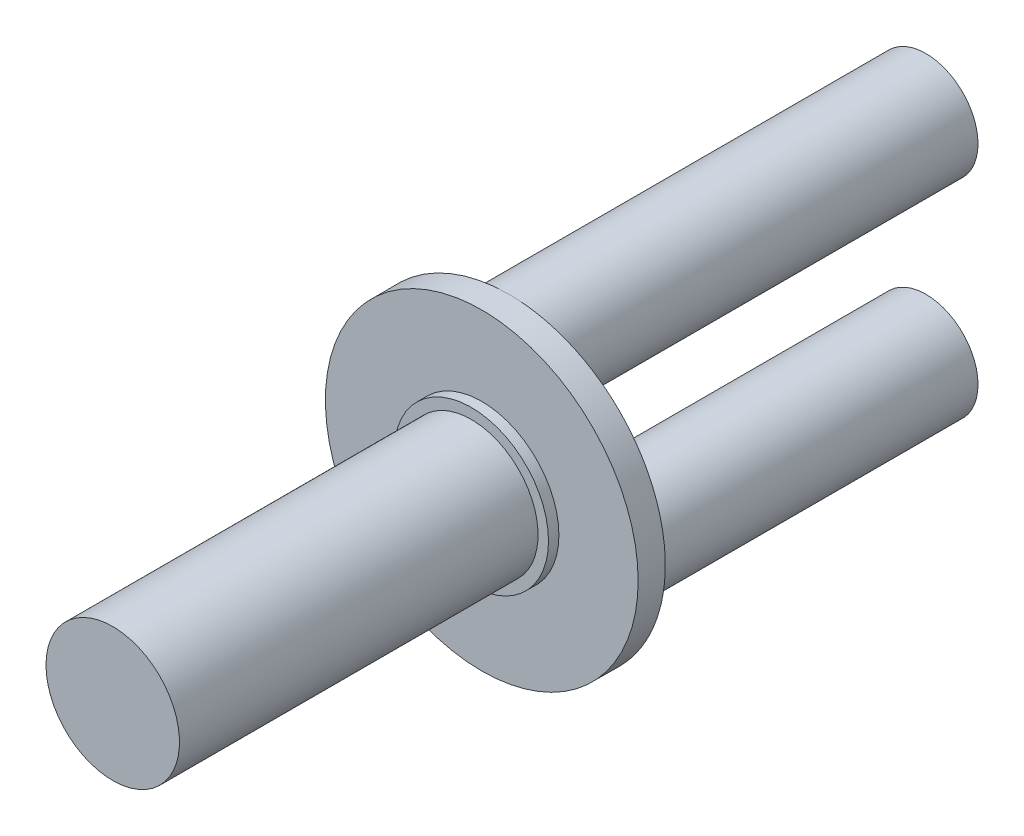
SolidWorks part; units mm, degrees
ref_plane "Front Plane" through (0, 0, 0) normal (0, 0, 1) x (1, 0, 0)
ref_plane "Top Plane" through (0, 0, 0) normal (0, 1, 0) x (1, 0, 0)
ref_plane "Right Plane" through (0, 0, 0) normal (1, 0, 0) x (0, 0, -1)
sketch "Sketch1" plane through (0, 0, 0) normal (0, 0, 1) x (1, 0, 0)
  line L0 (0, 0) -> (0, 19.05) construction
  circle A0 centre (0, 12.7) radius 1.5875
  circle A1 centre (0, 19.05) radius 1.5875
  dimension "D2" = 3.175
  dimension "D1" = 6.35
  dimension "D3" = 12.7
extrude "Boss-Extrude1" add sketch "Sketch1" against normal blind 12.7
sketch "Sketch2" plane through (0, 0, 0) normal (0, 0, 1) x (1, 0, 0)
  line L0 (0, 17.4625) -> (0, 14.2875) construction
  circle A0 centre (0, 15.875) radius 2.032
  circle A1 centre (0, 19.05) radius 1.5875 construction
  circle A2 centre (0, 12.7) radius 1.5875 construction
  dimension "D1" = 4.064
extrude "Boss-Extrude2" add sketch "Sketch2" along normal blind 12.065
ref_axis "Axis1" through (0, 15.875, 12.065) along (0, 0, -1)
sketch "Sketch3" plane through (0, 0, 0) normal (0, 0, 1) x (1, 0, 0)
  arc A3 (0.8604, 17.7159) -> (-0.8604, 17.7159) centre (0, 19.05) ccw construction
  circle A4 centre (0, 15.875) radius 4.7625
extrude "Boss-Extrude3" add sketch "Sketch3" along normal blind 0.8255
sketch "Sketch4" plane through (0, 0, 0.8255) normal (0, 0, 1) x (1, 0, 0)
  circle A0 centre (0, 15.875) radius 2.3495
  circle A1 centre (0, 15.875) radius 2.032 construction
  dimension "D1" = 0.3175
extrude "Boss-Extrude4" add sketch "Sketch4" along normal blind 0.3175
equation "\"D1@Sketch1\"=2*0.125"
